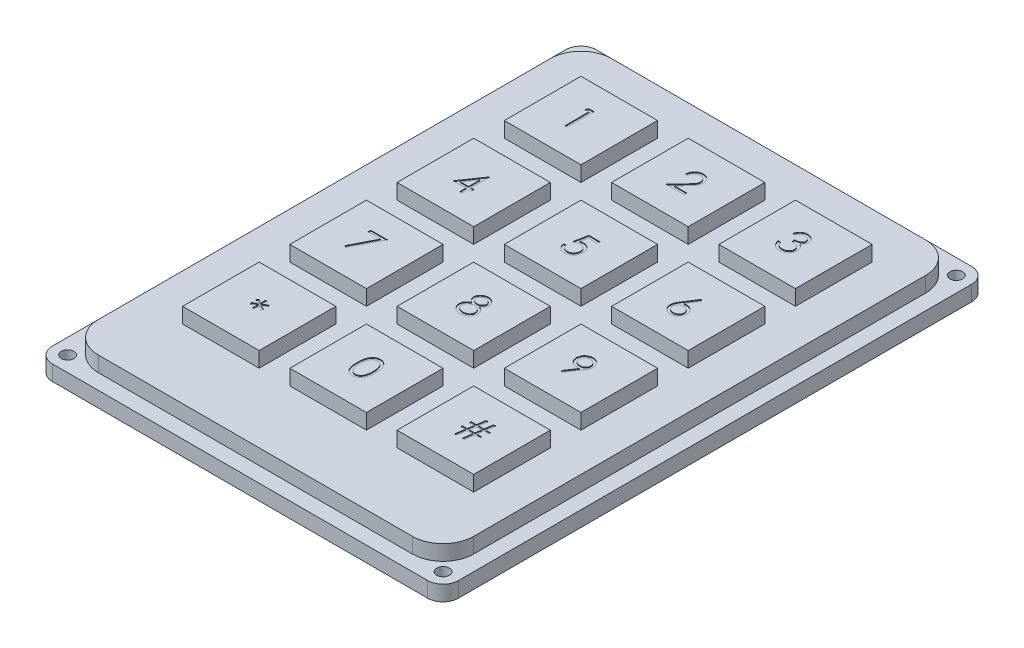
SolidWorks part; units mm, degrees
ref_plane "Front Plane" through (0, 0, 0) normal (0, 0, 1) x (1, 0, 0)
ref_plane "Top Plane" through (0, 0, 0) normal (0, 1, 0) x (1, 0, 0)
ref_plane "Right Plane" through (0, 0, 0) normal (1, 0, 0) x (0, 0, -1)
sketch "Sketch1" plane through (0, 0, 0) normal (0, 1, 0) x (1, 0, 0)
  line L1 (-26.5, -35.5) -> (26.5, -35.5)
  line L2 (-26.5, -35.5) -> (-26.5, 35.5)
  line L3 (-26.5, 35.5) -> (26.5, 35.5)
  line L4 (26.5, -35.5) -> (26.5, 35.5)
  line L5 (-26.5, -35.5) -> (26.5, 35.5) construction
  line L6 (-26.5, 35.5) -> (26.5, -35.5) construction
  point P0 (0, 0)
  dimension "D1" = 53
  dimension "D2" = 71
extrude "Boss-Extrude1" add sketch "Sketch1" along normal blind 2
fillet "Fillet1" radius 2 4 edges at (-26.5, 1, -35.5) (26.5, 1, -35.5) (26.5, 1, 35.5) (-26.5, 1, 35.5)
sketch "Sketch2" plane through (0, 2, 0) normal (0, 1, 0) x (1, 0, 0)
  line L4 (26.5, -33.5) -> (26.5, 33.5) construction
  line L5 (-24.5, -33.5) -> (24.5, -33.5)
  line L6 (-24.5, -33.5) -> (-24.5, 33.5)
  line L7 (-24.5, 33.5) -> (24.5, 33.5)
  line L8 (24.5, -33.5) -> (24.5, 33.5)
  line L9 (-24.5, -33.5) -> (24.5, 33.5) construction
  line L10 (-24.5, 33.5) -> (24.5, -33.5) construction
  line L11 (-24.5, -35.5) -> (24.5, -35.5) construction
  point P3 (0, 0)
  dimension "D1" = 2
  dimension "D2" = 2
extrude "Boss-Extrude2" add sketch "Sketch2" along normal blind 2
fillet "Fillet2" radius 4 4 edges at (24.5, 3, -33.5) (-24.5, 3, -33.5) (24.5, 3, 33.5) (-24.5, 3, 33.5)
sketch "Sketch3" plane through (0, 4, 0) normal (0, 1, 0) x (1, 0, 0)
  line L1 (-18.5, 17.5) -> (-8.5, 17.5)
  line L2 (-18.5, 17.5) -> (-18.5, 27.5)
  line L3 (-18.5, 27.5) -> (-8.5, 27.5)
  line L4 (-8.5, 17.5) -> (-8.5, 27.5)
  line L5 (-18.5, 17.5) -> (-8.5, 27.5) construction
  line L6 (-18.5, 27.5) -> (-8.5, 17.5) construction
  line L7 (-26.5, 33.5) -> (-26.5, -33.5) construction
  line L8 (24.5, 35.5) -> (-24.5, 35.5) construction
  point P0 (-13.5, 22.5)
  point P5 (-15.4887, 24.2408)
  dimension "D1" = 10
  dimension "D2" = 8
  dimension "D3" = 8
extrude "Key" add sketch "Sketch3" along normal blind 2
pattern_linear "Keys" count 3 spacing 14 along (1, 0, 0) count 4 spacing 14 along (0, 0, 1) of "Key"
sketch "Sketch4" plane through (0, 2, 0) normal (0, 1, 0) x (1, 0, 0)
  circle A0 centre (-24.5, 33.5) radius 0.8233
extrude "Cut-Extrude1" cut sketch "Sketch4" against normal through all
mirror "Mirror1" about plane through (0, 0, 0) normal (1, 0, 0) of "Cut-Extrude1"
mirror "Mirror2" about plane through (0, 0, 0) normal (0, 0, 1) of "Cut-Extrude1", "Mirror1"
sketch "Sketch5" plane through (0, 6, 0) normal (0, 1, 0) x (1, 0, 0)
  text T0 "1"
  text T1 "2"
  text T2 "3"
  text T3 "4"
  text T4 "5"
  text T5 "6"
  text T6 "7"
  text T7 "8"
  text T8 "9"
  text T9 "*"
  text T10 "0"
  text T11 "#"
  point P1 (-15.1679, 20.8513)
  point P3 (-0.8891, 20.8513)
  point P5 (12.8272, 20.8513)
  point P7 (-15.1679, 6.5403)
  point P9 (-0.8891, 6.5403)
  point P11 (12.8272, 6.5403)
  point P13 (-15.1679, -7.1135)
  point P15 (0, -7.1135)
  point P16 (-0.8891, -7.1135)
  point P18 (12.8272, -7.1135)
  point P20 (-15.1679, -22.3402)
  point P22 (-0.8891, -22.3402)
  point P23 (-0.8891, -21.1747)
  point P25 (12.8272, -21.1747)
  point P26 (-13.5213, -21.9896)
  point P27 (-14.6365, -22.0089)
  point P28 (0, 0)
extrude "Numbers" cut sketch "Sketch5" against normal blind 0.1
